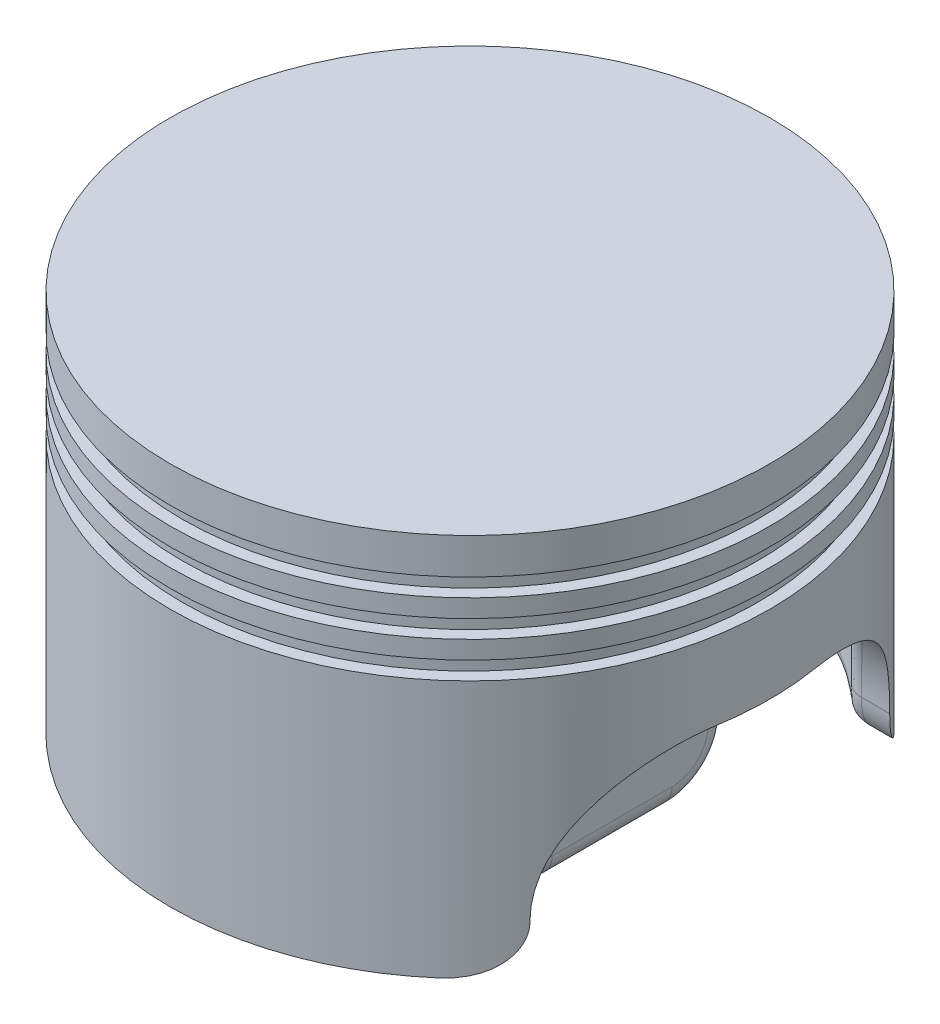
SolidWorks part; units mm, degrees
ref_plane "Front Plane" through (0, 0, 0) normal (0, 0, 1) x (1, 0, 0)
ref_plane "Top Plane" through (0, 0, 0) normal (0, 1, 0) x (1, 0, 0)
ref_plane "Right Plane" through (0, 0, 0) normal (1, 0, 0) x (0, 0, -1)
sketch "Sketch1" plane through (0, 0, 0) normal (1, 0, 0) x (0, 0, -1)
  line L0 (0, 0) -> (63.5, 0)
  line L1 (63.5, 0) -> (63.5, -81.28)
  line L2 (63.5, -81.28) -> (57.15, -81.28)
  line L3 (57.15, -81.28) -> (57.15, -19)
  line L4 (57.15, -19) -> (0, -19)
  line L5 (0, -19) -> (0, 0)
  point P3 (0, 0)
  point P9 (0, 0)
  dimension "D1" = 63.5
  dimension "D2" = 81.28
  dimension "D3" = 6.35
  dimension "D4" = 19
  dimension "D5" = 0
revolve "Revolve1" add sketch "Sketch1" angle 360 about L5
sketch "Sketch2" plane through (0, 0, 0) normal (0, 0, 1) x (1, 0, 0)
  line L0 (63.5, -7.62) -> (60.96, -7.62)
  line L1 (63.5, -81.28) -> (63.5, 0) construction
  line L2 (60.96, -7.62) -> (60.96, -11.43)
  line L3 (60.96, -11.43) -> (63.5, -11.43)
  line L4 (63.5, -11.43) -> (63.5, -7.62)
  line L5 (63.5, 0) -> (-63.5, 0) construction
  dimension "D1" = 3.81
  dimension "7" = 7.62
  dimension "D2" = 2.54
  dimension "D3" = 63.5
ref_axis "Axis1" through (0, 4.064, 0) along (0, -1, 0)
revolve "Cut-Revolve1" cut sketch "Sketch2" angle 360 about axis through (0, 4.064, 0) along (0, -1, 0)
ref_plane "Plane1" through (0, 10, 0) normal (0, 1, 0) x (1, 0, 0)
pattern_linear "LPattern1" count 3 spacing 7.62 along (0, -1, 0) of "Cut-Revolve1"
sketch "Sketch3" plane through (0, 0, 0) normal (1, 0, 0) x (0, 0, -1)
  line L0 (0, 4.064) -> (0, -85.344) construction
  line L1 (-38.1, -43.18) -> (38.1, -43.18)
  line L2 (-38.1, -43.18) -> (-38.1, -81.28)
  line L3 (-38.1, -81.28) -> (38.1, -81.28)
  line L4 (38.1, -43.18) -> (38.1, -81.28)
  line L5 (-38.1, -43.18) -> (38.1, -81.28) construction
  line L6 (-38.1, -81.28) -> (38.1, -43.18) construction
  line L7 (-57.15, -81.28) -> (57.15, -81.28) construction
  point P0 (0, -62.23)
  dimension "D1" = 76.2
  dimension "D2" = 38.1
extrude "Cut-Extrude1" cut sketch "Sketch3" against normal mid plane 281
fillet "Fillet2" radius 28 4 edges at (46.6985, -43.18, -38.1) (46.6985, -43.18, 38.1) (-46.6985, -43.18, 38.1) (-46.6985, -43.18, -38.1)
sketch "Sketch4" plane through (0, -19, 0) normal (0, -1, 0) x (1, 0, 0)
  line L1 (-34.88, -20.6067) -> (-15.88, -20.6067)
  line L2 (-34.88, -20.6067) -> (-34.88, 30.1933)
  line L3 (-34.88, 30.1933) -> (-15.88, 30.1933)
  line L4 (-15.88, -20.6067) -> (-15.88, 30.1933)
  line L5 (-34.88, -20.6067) -> (-15.88, 30.1933) construction
  line L6 (-34.88, 30.1933) -> (-15.88, -20.6067) construction
  point P0 (-25.38, 4.7933)
  dimension "D1" = 19
  dimension "15" = 15.88
  dimension "50.80" = 50.8
extrude "Boss-Extrude1" add sketch "Sketch4" along normal blind 63.5
mirror "Mirror1" about plane through (0, 0, 0) normal (1, 0, 0) of "Boss-Extrude1"
sketch "Sketch5" plane through (-34.88, 0, 0) normal (-1, 0, 0) x (0, 0, 1)
  line L0 (0, 4.064) -> (0, -85.344) construction
  line L1 (30.1933, -82.5) -> (-20.6067, -82.5) construction
  circle A0 centre (0, -57.1) radius 12.7
  dimension "D1" = 25.4
  dimension "D2" = 25.4
extrude "Cut-Extrude2" cut sketch "Sketch5" against normal blind 97.5
fillet "Fillet3" radius 12.7 4 edges at (25.38, -82.5, -20.6067) (25.38, -82.5, 30.1933) (-25.38, -82.5, 30.1933) (-25.38, -82.5, -20.6067)
fillet "Fillet4" radius 10 4 edges at (46.6985, -81.28, -38.1) (46.6985, -81.28, 38.1) (-46.6985, -81.28, 38.1) (-46.6985, -81.28, -38.1)
fillet "Fillet5" radius 5 20 edges at (34.88, -44.4, 30.1933) (34.88, -78.7803, 26.4736) (34.88, -44.4, -20.6067) (34.88, -78.7803, -16.8869) (15.88, -44.4, -20.6067) (15.88, -78.7803, -16.8869) (15.88, -44.4, 30.1933) (15.88, -78.7803, 26.4736) (-34.88, -44.4, 30.1933) (-34.88, -78.7803, 26.4736) (-34.88, -44.4, -20.6067) (-34.88, -78.7803, -16.8869) (-15.88, -44.4, -20.6067) (-15.88, -78.7803, -16.8869) (-15.88, -44.4, 30.1933) (-15.88, -78.7803, 26.4736) (34.88, -82.5, 4.7933) (15.88, -82.5, 4.7933) (-34.88, -82.5, 4.7933) (-15.88, -82.5, 4.7933)
fillet "Fillet6" radius 5 16 edges at (-41.3657, -76.2692, -39.4335) (-42.5971, -71.23, -38.1) (-50.4318, -48.7681, -26.8841) (-57.15, -43.18, 0) (-46.055, -56.3316, 33.8387) (-42.5971, -71.23, 38.1) (-40.0022, -78.1316, 40.816) (41.3657, -76.2692, 39.4335) (42.5971, -71.23, 38.1) (50.4318, -48.7681, 26.8841) (57.15, -43.18, 0) (46.055, -56.3316, -33.8387) (42.5971, -71.23, -38.1) (40.0022, -78.1316, -40.816) (0, -81.28, 57.15) (0, -81.28, -57.15)
